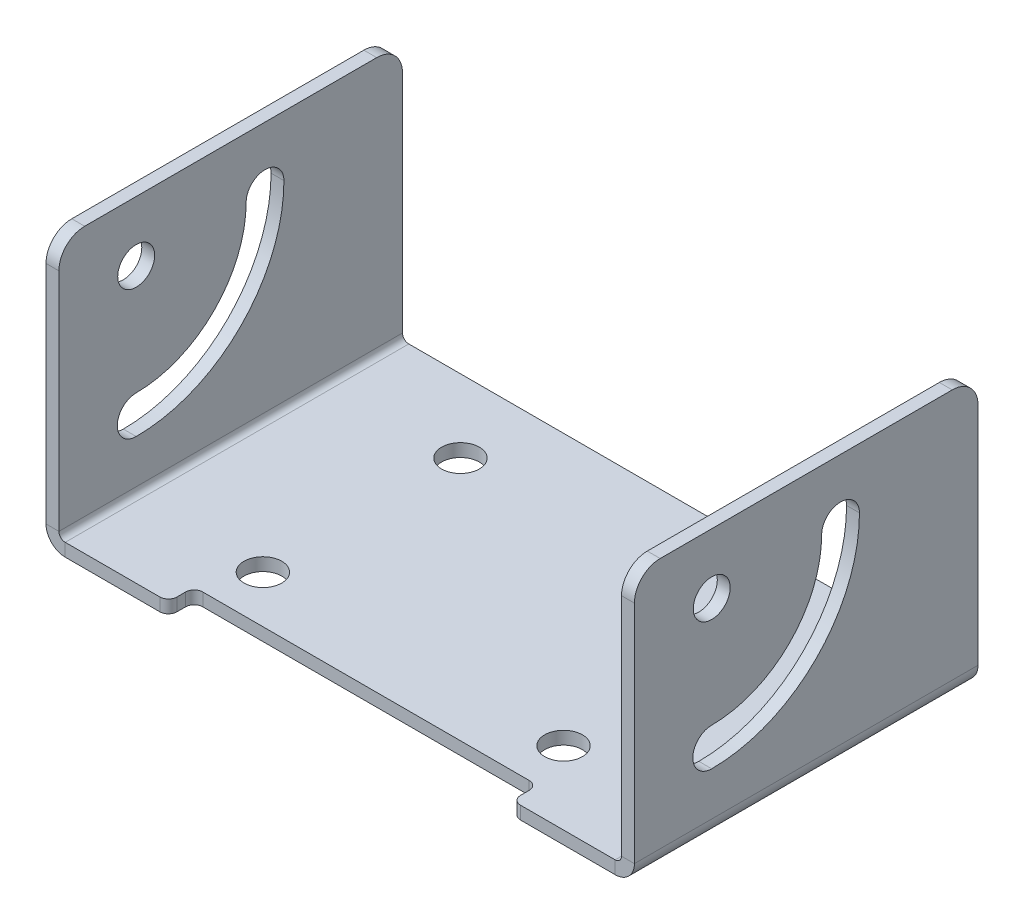
SolidWorks part; units mm, degrees
note: The reader was unsure of these and kept them because the rebuilt part matched: flange length of "边线-法兰1".
ref_plane "前视基准面" through (0, 0, 0) normal (0, 0, 1) x (1, 0, 0)
ref_plane "上视基准面" through (0, 0, 0) normal (0, 1, 0) x (1, 0, 0)
ref_plane "右视基准面" through (0, 0, 0) normal (1, 0, 0) x (0, 0, -1)
sketch "草图1" plane through (0, 0, 0) normal (0, 1, 0) x (1, 0, 0)
  line L0 (-32.75, 20) -> (32.75, 20)
  line L1 (-32.75, -20) -> (32.75, -20)
  line L2 (-32.75, -20) -> (-32.75, 20)
  line L4 (32.75, -20) -> (32.75, 20)
  line L5 (-32.75, -20) -> (32.75, 20) construction
  line L6 (-32.75, 20) -> (32.75, -20) construction
  line L7 (-17.5, -11.5) -> (17.5, -11.5) construction
  line L8 (-17.5, -11.5) -> (-17.5, 11.5) construction
  line L9 (-17.5, 11.5) -> (17.5, 11.5) construction
  line L10 (17.5, -11.5) -> (17.5, 11.5) construction
  line L11 (-17.5, -11.5) -> (17.5, 11.5) construction
  line L12 (-17.5, 11.5) -> (17.5, -11.5) construction
  circle A0 centre (-17.5, 11.5) radius 2.2
  circle A1 centre (17.5, 11.5) radius 2.2
  circle A2 centre (17.5, -11.5) radius 2.2
  circle A3 centre (-17.5, -11.5) radius 2.2
  point P0 (0, 0)
  point P6 (0, 0)
  dimension "D3" = 4.4
  dimension "D1" = 65.5
  dimension "D2" = 40
  dimension "D4" = 35
  dimension "D5" = 23
base flange "基体-法兰1" sketch "草图1" thickness 1.5 reverse thickness direction no parameters "D1"=0.7366
edge flange "边线-法兰1" sketch "草图10" flange profiles "草图10", "草图11" flange angle 90 flange length 30 flange position material outside bend radius 0.7366 thickness 1.5 relief rectangular parameters "D6"=10, "D8"=1
sketch "草图10" plane through (-32.75, 0, 0) normal (-1, 0, 0) x (0, 0, 1)
  line L0 (-20, 0) -> (20, 0) construction
  line L1 (-20, 0) -> (20, 0)
  line L2 (-20, 0) -> (-20, 30)
  line L3 (-20, 30) -> (20, 30)
  line L4 (20, 30) -> (20, 0)
sketch "草图11" plane through (32.75, 0, 0) normal (1, 0, 0) x (0, 0, -1)
  line L0 (-20, 0) -> (20, 0) construction
  line L1 (-20, 0) -> (20, 0)
  line L2 (-20, 0) -> (-20, 30)
  line L3 (-20, 30) -> (20, 30)
  line L4 (20, 30) -> (20, 0)
bend "边线折弯1" bend radius 0.7366 bend angle 90 parameters "D5"=1
bend "边线折弯2" bend radius 0.7366 bend angle 90 parameters "D5"=2
sketch "草图12" plane through (-34.25, 0, 0) normal (-1, 0, 0) x (0, 0, 1)
  line L0 (11, 23) -> (11, 3.6999) construction
  line L1 (20, 0.7366) -> (20, 30) construction
  line L2 (20, 30) -> (-20, 30) construction
  circle A0 centre (11, 23) radius 2.15
  arc A1 (-4, 23) -> (11, 8) centre (11, 23) ccw construction
  arc A2 (-6.2, 23) -> (11, 5.8) centre (11, 23) ccw
  arc A3 (-1.8, 23) -> (11, 10.2) centre (11, 23) ccw
  arc A4 (-1.8, 23) -> (-6.2, 23) centre (-4, 23) ccw
  arc A5 (11, 5.8) -> (11, 10.2) centre (11, 8) ccw
  point P4 (0.3934, 12.3934)
  dimension "D1" = 15
  dimension "D2" = 2.2
  dimension "D4" = 4.3
  dimension "D3" = 90
  dimension "D5" = 9
  dimension "D6" = 7
extrude "切除-拉伸1" cut sketch "草图12" against normal through all normal cut yes
sketch "草图13" plane through (0, 0, 0) normal (0, 1, 0) x (1, 0, 0)
  line L0 (-32.0134, -20) -> (32.0134, -20) construction
  line L1 (-20, -20) -> (20, -20)
  line L2 (-20, -20) -> (-20, -17)
  line L3 (-20, -17) -> (20, -17)
  line L4 (20, -20) -> (20, -17)
  point P6 (0, -20)
  dimension "D1" = 40
  dimension "D2" = 3
extrude "切除-拉伸2" cut sketch "草图13" against normal through all normal cut yes
fillet "圆角1" radius 1 4 edges at (20, -0.75, 20) (20, -0.75, 17) (-20, -0.75, 20) (-20, -0.75, 17)
fillet "圆角2" radius 3 4 edges at (-33.5, 30, 20) (-33.5, 30, -20) (33.5, 30, 20) (33.5, 30, -20)
sketch "折弯-线1" [suppressed] plane through (0, 0, 0) normal (0, 1, 0) x (1, 0, 0)
sketch "边界框1" [suppressed] plane through (0, 0, 0) normal (0, 1, 0) x (1, 0, 0)
sheet metal parameters "钣金6" thickness 1.5 parameters "D1"=0.7366
flat pattern "平板型式6" [suppressed]
sketch "折弯-线2" plane through (0, 0, 0) normal (0, 1, 0) x (1, 0, 0)
sketch "边界框2" [suppressed] plane through (0, 0, 0) normal (0, 1, 0) x (1, 0, 0)
sheet metal parameters "钣金7" thickness 1.5 parameters "D1"=0.7366
flat pattern "平板型式6" [suppressed]
sketch "折弯-线2" plane through (0, 0, 0) normal (0, 1, 0) x (1, 0, 0)
sketch "边界框2" [suppressed] plane through (0, 0, 0) normal (0, 1, 0) x (1, 0, 0)
bend of the flat pattern "展平-<边线折弯1>1"
bend of the flat pattern "展平-<边线折弯2>1"
sheet metal parameters "钣金8" thickness 1.5 parameters "D1"=0.7366
flat pattern "平板型式6"
sketch "折弯-线2" plane through (0, 0, 0) normal (0, 1, 0) x (1, 0, 0)
  line L0 (33.181, -20) -> (33.181, 20) construction
  line L1 (-33.181, 20) -> (-33.181, -20) construction
  line L2 (33.181, -20) -> (33.181, 20) construction
  line L3 (-33.181, 20) -> (-33.181, -20) construction
sketch3d "边界框2" [suppressed]
  line L0 (63.6119, 20, 0) -> (-63.6119, 20, 0) construction
  line L1 (63.6119, -20, 0) -> (-63.6119, -20, 0) construction
  line L2 (63.6119, 20, 0) -> (63.6119, -20, 0) construction
  line L3 (-63.6119, 20, 0) -> (-63.6119, -20, 0) construction
bend of the flat pattern "展平-<边线折弯1>1"
bend of the flat pattern "展平-<边线折弯2>1"
sheet metal parameters "钣金9" thickness 1.5 parameters "D1"=0.7366
flat pattern "平板型式6"
sketch "折弯-线2" plane through (0, 0, 0) normal (0, 1, 0) x (1, 0, 0)
  line L0 (33.181, -20) -> (33.181, 20) construction
  line L1 (-33.181, 20) -> (-33.181, -20) construction
  line L2 (33.181, -20) -> (33.181, 20) construction
  line L3 (-33.181, 20) -> (-33.181, -20) construction
sketch3d "边界框2" [suppressed]
  line L0 (63.6119, 80, 0) -> (-63.6119, 80, 0) construction
  line L1 (63.6119, -20, 0) -> (-63.6119, -20, 0) construction
  line L2 (63.6119, 80, 0) -> (63.6119, -20, 0) construction
  line L3 (-63.6119, 80, 0) -> (-63.6119, -20, 0) construction
bend of the flat pattern "展平-<边线折弯1>1"
bend of the flat pattern "展平-<边线折弯2>1"
